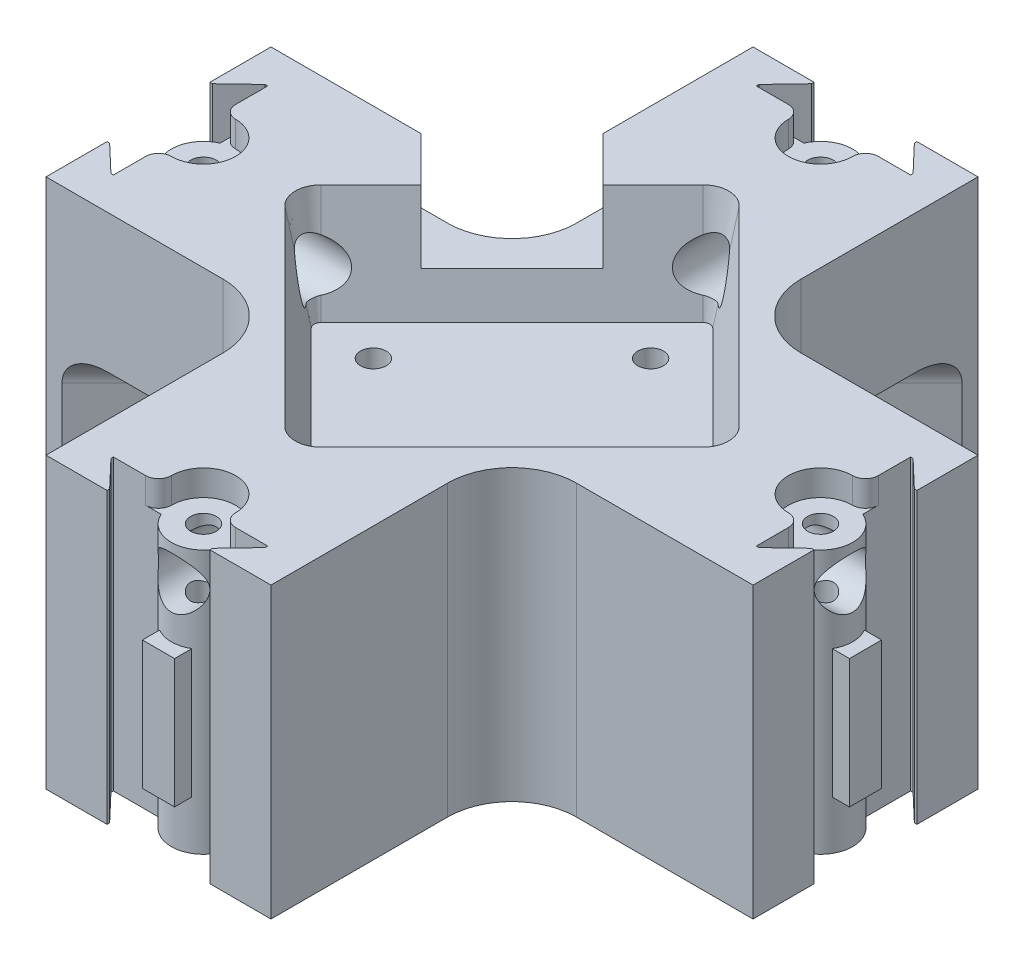
SolidWorks part; units mm, degrees
ref_plane "Front Plane" through (0, 0, 0) normal (0, 0, 1) x (1, 0, 0)
ref_plane "Top Plane" through (0, 0, 0) normal (0, 1, 0) x (1, 0, 0)
ref_plane "Right Plane" through (0, 0, 0) normal (1, 0, 0) x (0, 0, -1)
sketch "Sketch1" plane through (0, 0, 0) normal (0, 1, 0) x (1, 0, 0)
  line L0 (17.4176, 71.3548) -> (17.4176, 43.8548)
  line L1 (17.4176, -38.6452) -> (-17.5824, -38.6452)
  line L2 (-17.5824, 43.8548) -> (-17.5824, 71.3548)
  line L3 (-17.5824, 71.3548) -> (17.4176, 71.3548)
  line L4 (-17.5824, -38.6452) -> (-17.5824, -11.1452)
  line L5 (-27.5824, -1.1452) -> (-55.0824, -1.1452)
  line L6 (-55.0824, -1.1452) -> (-55.0824, 33.8548)
  line L7 (-55.0824, 33.8548) -> (-27.5824, 33.8548)
  line L8 (-17.5824, 33.8548) -> (17.4176, 33.8548)
  line L9 (27.4176, 33.8548) -> (54.9176, 33.8548)
  line L10 (54.9176, 33.8548) -> (54.9176, -1.1452)
  line L11 (54.9176, -1.1452) -> (27.4176, -1.1452)
  line L12 (17.4176, -1.1452) -> (-17.5824, 33.8548)
  line L13 (17.4176, 33.8548) -> (-17.5824, -1.1452)
  line L14 (-0.0824, 16.3548) -> (27.6715, 44.1087)
  line L15 (10.1706, 61.6096) -> (45.1724, 26.6079)
  line L16 (-45.3373, 6.1018) -> (-10.3355, -28.9)
  line L17 (17.4176, 68.8566) -> (-52.5842, -1.1452)
  line L18 (52.4193, 33.8548) -> (-17.5824, -36.147)
  line L19 (17.4176, -38.6452) -> (17.4176, -11.1452)
  arc A0 (-27.5824, 33.8548) -> (-17.5824, 43.8548) centre (-27.5824, 43.8548) ccw
  arc A1 (-17.5824, -11.1452) -> (-27.5824, -1.1452) centre (-27.5824, -11.1452) ccw
  arc A2 (17.4176, 43.8548) -> (27.4176, 33.8548) centre (27.4176, 43.8548) ccw
  arc A3 (27.4176, -1.1452) -> (17.4176, -11.1452) centre (27.4176, -11.1452) ccw
  dimension "D1" = 10
  dimension "D4" = 10
  dimension "D5" = 10
  dimension "D6" = 10
  dimension "D2" = 39.25
  dimension "D3" = 49.5
extrude "Boss-Extrude1" add sketch "Sketch1" along normal blind 45 contours A0 L7 L6 L5 L17 L0 L3 L2 | L16 L17 L5 | A2 L0 L15 L17 L16 L5 A1 L4 L18 L9 L13 L12 L8 | L13 L8 L12 | L0 L17 L15 | L18 L9 L15 | A3 L11 L10 L9 L18 L4 L1 L19 | L18 L16 L4 region at (16.3922, 0, -70.1057) region at (15.0019, 0, -61.6096) region at (-0.0824, 0, -28.0215) region at (-0.0824, 0, -15.2389) region at (-45.3373, 0, -1.2705) region at (45.1724, 0, -31.4392) region at (53.6684, 0, -32.8295) region at (-15.1668, 0, 28.9)
extrude "Cut-Extrude1" cut sketch "Sketch1<3>" along normal blind 34.5 contours L16 L17 L5 | A2 L0 L15 L17 L16 L5 A1 L4 L18 L9 L13 L12 L8 | L18 L16 L4 | L13 L8 L12 | L0 L17 L15 | L18 L9 L15 region at (15.0019, 0, -61.6096) region at (-0.0824, 0, -28.0215) region at (-0.0824, 0, -15.2389) region at (-45.3373, 0, -1.2705) region at (45.1724, 0, -31.4392) region at (-15.1668, 0, 28.9)
sketch "Sketch1<3>" plane through (0, 0, 0) normal (0, 1, 0) x (1, 0, 0) same geometry as "Sketch1"
ref_plane "Plane1" through (0, 0, -16.3548) normal (0, 0, 1) x (1, 0, 0)
sketch "Sketch3" plane through (0, 45, 0) normal (0, 1, 0) x (1, 0, 0)
  line L0 (-55.0824, 8.3548) -> (-55.0824, 24.3548)
  line L1 (-55.0824, -1.1452) -> (-55.0824, 33.8548) construction
  line L2 (-55.0824, 24.3548) -> (-54.6824, 24.3548)
  line L3 (-55.0824, 16.3548) -> (-50.0824, 16.3548)
  line L4 (-24.75, 16.3548) -> (24.75, 16.3548) construction
  line L5 (-50.0824, 4.3548) -> (-50.0824, 28.3548)
  line L6 (-50.0824, 28.3548) -> (-50.4824, 28.3548)
  line L7 (-50.4824, 28.3548) -> (-54.6824, 24.3548)
  line L8 (-50.0824, 4.3548) -> (-50.4824, 4.3548)
  line L9 (-55.0824, 8.3548) -> (-54.6824, 8.3548)
  line L10 (-50.4824, 4.3548) -> (-54.6824, 8.3548)
  line L11 (-50.0824, 16.3548) -> (-48.0824, 16.3548)
  line L14 (-48.0824, 11.3548) -> (-48.0824, 9.3548)
  circle A0 centre (-48.0824, 16.3548) radius 2
  arc A1 (-48.0824, 11.3548) -> (-48.0824, 21.3548) centre (-48.0824, 16.3548) ccw
  circle A2 centre (-48.0824, 9.3548) radius 2
  circle A3 centre (-48.0824, 23.3548) radius 2
  line M27 (-55.0824, 33.8548) -> (-55.0824, -1.1452)
  dimension "D1" = 0.4
  dimension "D5" = 5
  dimension "D6" = 4
  dimension "D2" = 0.4
  dimension "D3" = 24
  dimension "D4" = 16
ref_plane "Plane3" through (-0.0824, 0, 0) normal (1, 0, 0) x (0, 0, -1)
ref_axis "Axis1" through (-0.0824, -2.25, -16.3548) along (0, 1, 0)
ref_axis "Axis2" through (20.3465, 45, -36.7837) along (-0.7071, 0, 0.7071)
extrude "Cut-Extrude2" cut sketch "Sketch3" against normal through all contours L10 L8 L5 L3 L0 L9 | L6 L7 L2 L3 L5 M27 region at (-52.3912, 45, -11.2668) region at (-52.3912, 45, -21.4428)
extrude "Cut-Extrude3" cut sketch "Sketch3<3>" against normal blind 4 contours A1 A3 L5 A0 A2 | A0 region at (-49.9259, 45, -19.8548) region at (-48.0824, 45, -18.2982)
sketch "Sketch3<3>" plane through (0, 45, 0) normal (0, 1, 0) x (1, 0, 0) same geometry as "Sketch3"
pattern_circular "CirPattern1" count 4 over 360 about axis through (-0.0824, -2.25, -16.3548) along (0, 1, 0) of "Cut-Extrude3", "Cut-Extrude2"
sketch "Sketch5" plane through (0, 0, 33.6452) normal (0, 0, 1) x (1, 0, 0)
  line L0 (-0.0824, 45) -> (-0.0824, 44.05)
  line L1 (-0.0824, -2.25) -> (-0.0824, 47.25) construction
  line L2 (20.3465, 45) -> (-20.5114, 45) construction
  line L3 (-0.0824, -24.75) -> (-0.0824, 24.75) construction
  line L4 (-0.0824, 45) -> (-0.0824, 35.6)
  line L5 (-0.0824, 31.6) -> (-0.0824, 27.6)
  line L6 (-2.5824, 27.6) -> (2.4176, 27.6)
  line L7 (2.4176, 27.6) -> (2.4176, 7.6)
  line L8 (-2.5824, 27.6) -> (-2.5824, 7.6)
  line L9 (2.4176, 7.6) -> (-2.5824, 7.6)
  circle A0 centre (-0.0824, 35.6) radius 4
  dimension "D1" = 9.4
  dimension "D3" = 8
  dimension "D2" = 4
  dimension "D4" = 2.5
  dimension "D5" = 20
extrude "Boss-Extrude2" add sketch "Sketch5" along normal blind 4 contours L9 L7 L6 L8 region at (-0.0824, 17.6, 33.6452)
sketch "Sketch6" plane through (0, 45, 0) normal (0, 1, 0) x (1, 0, 0)
  line L0 (-20.5114, 36.7837) -> (20.3465, -4.0741)
  line L1 (20.3465, 36.7837) -> (-20.5114, -4.0741)
  line L2 (-0.0824, 16.3548) -> (-17.7601, 34.0325)
  line L3 (-17.7601, 34.0325) -> (-2.9109, 48.8817)
  line L4 (2.746, 48.8817) -> (32.4445, 19.1832)
  line L5 (-17.7601, 34.0325) -> (-32.6094, 19.1832)
  line L6 (-32.6094, 13.5264) -> (-2.9109, -16.1721)
  line L7 (2.746, -16.1721) -> (32.4445, 13.5264)
  arc A0 (-27.5824, 33.8548) -> (-17.5824, 43.8548) centre (-27.5824, 43.8548) ccw construction
  arc A1 (27.4176, -1.1452) -> (17.4176, -11.1452) centre (27.4176, -11.1452) ccw construction
  arc A2 (17.4176, 43.8548) -> (27.4176, 33.8548) centre (27.4176, 43.8548) ccw construction
  arc A3 (-17.5824, -11.1452) -> (-27.5824, -1.1452) centre (-27.5824, -11.1452) ccw construction
  arc A4 (-32.6094, 19.1832) -> (-32.6094, 13.5264) centre (-29.7809, 16.3548) ccw
  arc A5 (-2.9109, -16.1721) -> (2.746, -16.1721) centre (-0.0824, -13.3437) ccw
  arc A6 (32.4445, 19.1832) -> (32.4445, 13.5264) centre (29.616, 16.3548) cw
  arc A7 (-2.9109, 48.8817) -> (2.746, 48.8817) centre (-0.0824, 46.0533) cw
  circle A8 centre (47.9176, 16.3548) radius 2
  circle A9 centre (47.9176, 16.3548) radius 5
  point P24 (-35.4378, 16.3548)
  point P29 (35.2729, 16.3548)
  point P32 (-0.0824, 51.7101)
  dimension "D5" = 4
  dimension "D1" = 25
  dimension "D2" = 25
  dimension "D3" = 50
  dimension "D4" = 25
extrude "Boss-Extrude3" add sketch "Sketch6" against normal through all contours A9 A8 region at (43.059, 45, -16.3548)
extrude "Cut-Extrude4" cut sketch "Sketch6<4>" against normal blind 4 contours A9 A8 region at (43.059, 45, -16.3548)
sketch "Sketch6<4>" plane through (0, 45, 0) normal (0, 1, 0) x (1, 0, 0) same geometry as "Sketch6"
extrude "Cut-Extrude5" cut sketch "Sketch6<5>" against normal through all contours A8 region at (47.9176, 45, -16.3548)
sketch "Sketch6<5>" plane through (0, 45, 0) normal (0, 1, 0) x (1, 0, 0) same geometry as "Sketch6"
extrude "Boss-Extrude5" add sketch "Sketch5<3>" along normal blind 5 contours L7 L9 L8 L6
sketch "Sketch5<3>" plane through (0, 0, 33.6452) normal (0, 0, 1) x (1, 0, 0) same geometry as "Sketch5"
pattern_circular "CirPattern5" count 4 over 360 about axis through (-0.0824, -2.25, -16.3548) along (0, 1, 0) of "Cut-Extrude5", "Boss-Extrude3", "Cut-Extrude4"
pattern_circular "CirPattern6" count 4 over 360 about axis through (-0.0824, -2.25, -16.3548) along (0, 1, 0) of "Boss-Extrude5"
sketch "Sketch12" plane through (0, 34.5, 0) normal (0, -1, 0) x (1, 0, 0)
  line L0 (52.4193, -33.8548) -> (-17.5824, 36.147)
  line L1 (-17.5824, 36.147) -> (-17.5824, 11.1452)
  line L2 (-52.5842, 1.1452) -> (-27.5824, 1.1452)
  line L4 (-52.5842, 1.1452) -> (17.4176, -68.8566)
  line L5 (17.4176, -68.8566) -> (17.4176, -43.8554)
  line L6 (27.4173, -33.8554) -> (52.4193, -33.8548)
  arc A1 (-17.5824, 11.1452) -> (-27.5824, 1.1452) centre (-27.5824, 11.1452) cw
  arc A2 (17.4176, -43.8554) -> (27.4173, -33.8554) centre (27.4176, -43.8554) cw
  dimension "D1" = 10
  dimension "D2" = 10
extrude "Boss-Extrude6" add sketch "Sketch12" along normal blind 11
ref_axis "Axis3" through (20.3464, 23.5, -36.7845) along (-0.7071, 0, 0.7071)
ref_plane "Plane4" through (-8.2193, 0.0003, -8.2191) normal (-0.7071, 0, -0.7071) x (-0.7071, 0, 0.7071)
extrude "Cut-Extrude6" cut sketch "Sketch6<7>" against normal blind 16.5 draft 10 contours A7 L3 L0 L1 L4 | A6 L4 L1 L0 L7 | L5 A4 L6 L1 L0 | L6 A5 L7 L0 L1 region at (-0.0824, 45, -33.9418) region at (-17.6694, 45, -16.3548) region at (17.5045, 45, -16.3548) region at (-0.0824, 45, 1.2322)
sketch "Sketch6<7>" plane through (0, 45, 0) normal (0, 1, 0) x (1, 0, 0) same geometry as "Sketch6"
extrude "Cut-Extrude8" cut sketch "Sketch5<7>" against normal through all and the other way through all contours A0
sketch "Sketch5<7>" plane through (0, 0, 33.6452) normal (0, 0, 1) x (1, 0, 0) same geometry as "Sketch5"
mirror "Mirror2" about plane through (-8.2193, 0.0003, -8.2191) normal (-0.7071, 0, -0.7071) of "Cut-Extrude8"
fillet "Fillet2" radius 5 2 edges at (-17.5833, 23.5, -33.8557) (17.4184, 23.5, 1.1461)
sketch "Sketch14" plane through (0, 28.5, 0) normal (0, 1, 0) x (1, 0, 0)
  line L0 (-0.0824, 47.1439) -> (-0.0824, -14.4343)
  line L1 (-30.8715, 16.3548) -> (30.7066, 16.3548)
  line L2 (-0.0824, 16.3548) -> (10.7009, 5.5714)
  line L3 (10.7009, 5.5714) -> (21.4843, 16.3548)
  arc A4 (0.6887, 46.8245) -> (-0.8536, 46.8245) centre (-0.0824, 46.0533) ccw construction
  arc A5 (-0.8536, -14.1149) -> (0.6887, -14.1149) centre (-0.0824, -13.3437) ccw construction
  arc A6 (30.3872, 15.5836) -> (30.3872, 17.126) centre (29.616, 16.3548) ccw construction
  circle A7 centre (21.4843, 16.3548) radius 2
  circle A8 centre (-0.0824, -5.212) radius 2
  circle A9 centre (-21.6492, 16.3548) radius 2
  circle A10 centre (-0.0824, 37.9216) radius 2
  point P14 (-0.0824, 16.3548)
  point P27 (-0.0824, 16.3548)
  dimension "D1" = 4
  dimension "D4" = 4
  dimension "D2" = 15.25
  dimension "D3" = 15.25
extrude "Cut-Extrude9" cut sketch "Sketch14" against normal through all contours A10 | A9 | A8 | A7
ref_plane "Plane7" through (-25.7195, 0, -25.7195) normal (0.7071, 0, 0.7071) x (0.7071, 0, -0.7071)
sketch "Sketch17" plane through (-25.7195, 0, -25.7195) normal (0.7071, 0, 0.7071) x (0.7071, 0, -0.7071)
  line L0 (-9.4937, 45) -> (32.5063, 45) construction
  line L1 (1.5063, 55) -> (21.5063, 55)
  line L2 (1.5063, 55) -> (1.5063, 35)
  line L3 (1.5063, 35) -> (21.5063, 35)
  line L4 (21.5063, 55) -> (21.5063, 35)
  line L5 (11.5063, 35) -> (11.5063, 55) construction
  line L6 (1.5063, 45) -> (21.5063, 45) construction
  point P0 (11.5063, 45)
  dimension "D1" = 20
  dimension "D2" = 20
extrude "Cut-Extrude11" cut sketch "Sketch17" against normal blind 15 and the other way blind 10 contours L2 L1 L4 L3
